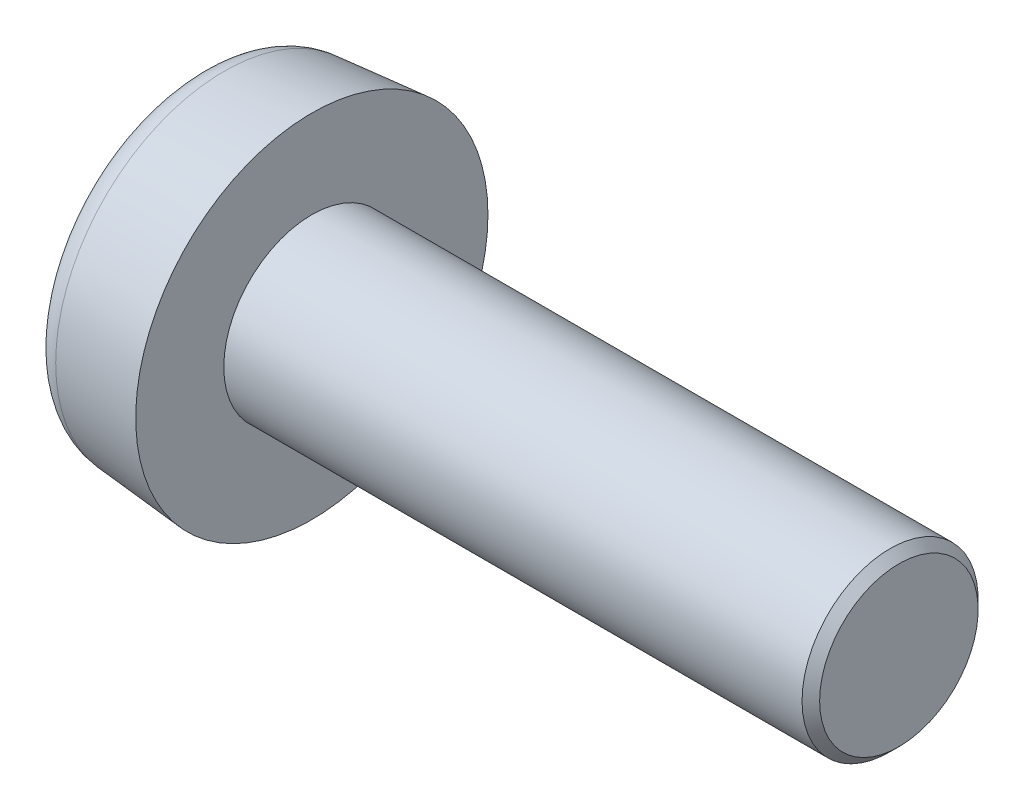
SolidWorks part; units mm, degrees
ref_plane "Front" through (0, 0, 0) normal (0, 0, 1) x (1, 0, 0)
ref_plane "Top" through (0, 0, 0) normal (0, 1, 0) x (1, 0, 0)
ref_plane "Right" through (0, 0, 0) normal (1, 0, 0) x (0, 0, -1)
ref_plane "Plane1" through (3.9, 0, 0) normal (1, 0, 0) x (0, 0, -1)
sketch "Sketch1" plane through (3.9, 0, 0) normal (1, 0, 0) x (0, 0, -1)
  circle A0 centre (0, 0) radius 6
  dimension "dk" = 12
extrude "BaseHead" add sketch "Sketch1" against normal blind 3.9 draft 5
sketch "Sketch2" plane through (3.9, 0, 0) normal (1, 0, 0) x (0, 0, -1)
  circle A0 centre (0, 0) radius 3
extrude "BaseBody" add sketch "Sketch2" along normal blind 20
cosmetic thread "ThreadCosmetic1" [suppressed] parameters "bb"=19.9, "THD_MINOR"=5
fillet "HeadFillet" [suppressed] radius 0.1
sketch "Sketch3" plane through (0, 0, 0) normal (1, 0, 0) x (0, 0, -1)
  line L1 (2.396, 0) -> (1.198, 2.075)
  line L2 (1.198, 2.075) -> (-1.198, 2.075)
  line L3 (-1.198, 2.075) -> (-2.396, 0)
  line L4 (-2.396, 0) -> (-1.198, -2.075)
  line L5 (-1.198, -2.075) -> (1.198, -2.075)
  line L6 (1.198, -2.075) -> (2.396, 0)
  circle A0 centre (0, 0) radius 2.075 construction
  dimension "B" = 4.15
extrude "HexagonSocket" cut sketch "Sketch3" along normal blind 2
sketch "Sketch4" plane through (2, 0, 0) normal (-1, 0, 0) x (0, 0, 1)
  line L0 (1.198, -2.075) -> (-1.198, -2.075) construction
  line L1 (-1.198, -2.075) -> (-2.396, 0) construction
  line L2 (-2.396, 0) -> (-1.198, 2.075) construction
  line L3 (2.396, 0) -> (1.198, -2.075) construction
  line L4 (1.198, 2.075) -> (2.396, 0) construction
  line L5 (-1.198, 2.075) -> (1.198, 2.075) construction
  line L6 (1.198, -2.075) -> (-1.198, -2.075)
  line L7 (-1.198, -2.075) -> (-2.396, 0)
  line L8 (-2.396, 0) -> (-1.198, 2.075)
  line L9 (2.396, 0) -> (1.198, -2.075)
  line L10 (1.198, 2.075) -> (2.396, 0)
  line L11 (-1.198, 2.075) -> (1.198, 2.075)
extrude "Cut-Extrude2" cut sketch "Sketch4" against normal blind 5 draft 60
fillet "TopFillet" radius 1 1 edges at (0, 0, -5.6588)
chamfer "Chamfer1" distance 0.3 angle 45 1 edges at (23.9, 0, -3)
sketch "Sketch5" plane through (0, 0, 0) normal (0, 0, 1) x (1, 0, 0)
  line L0 (23.6, 2.567) -> (23.85, 3)
  line L1 (23.85, 3) -> (23.85, 3.5)
  line L2 (23.85, 3.5) -> (23.35, 3.5)
  line L3 (23.35, 3.5) -> (23.35, 3)
  line L4 (23.35, 3) -> (23.6, 2.567)
  line L5 (0, 0) -> (26.2596, 0) construction
  line L6 (23.6, -3) -> (23.6, 3) construction
  dimension "D1" = 0.5
  dimension "D2" = 6
revolve "Cut-Revolve10" [suppressed] cut sketch "Sketch5" angle 360 about L5
pattern_linear "LPattern10" [suppressed] count 33 spacing 0.6 along (-1, 0, 0) of bodies 105
equation "\"D1@Plane1\" = \"K@BaseHead\""
equation "\"D2@Sketch5\" = \"d@Sketch2\""
equation "\"D1@Sketch5\" =  ( \"d@Sketch2\" - \"THD_MINOR@ThreadCosmetic1\" )  / 2"
equation "\"D3@LPattern10\" = \"D1@Sketch5\" * 1.2"
equation "\"D1@LPattern10\" = \"bb@ThreadCosmetic1\" / \"D3@LPattern10\""
